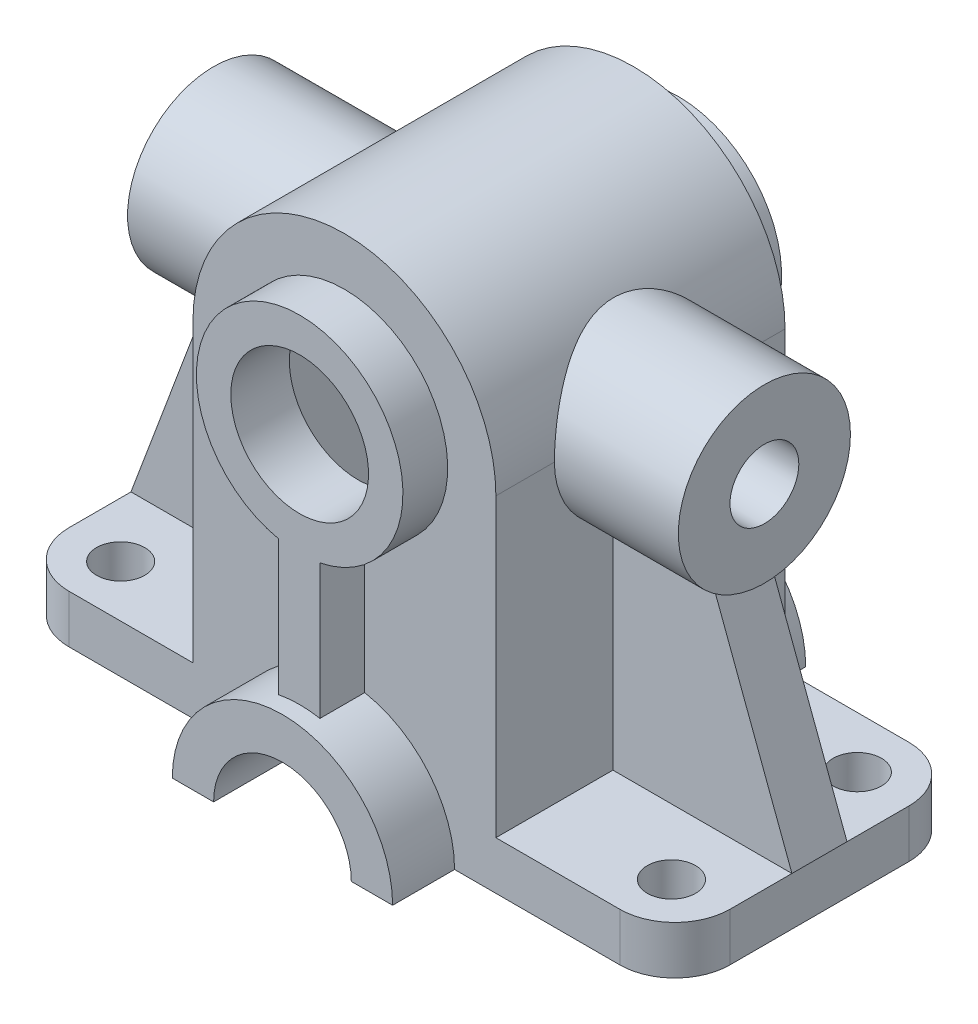
SolidWorks part; units mm, degrees
note: The reader was unsure of these and kept them because the rebuilt part matched: shared geometry of "Sketch5<3>", "Sketch1<3>".
ref_plane "Front Plane" through (0, 0, 0) normal (0, 0, 1) x (1, 0, 0)
ref_plane "Top Plane" through (0, 0, 0) normal (0, 1, 0) x (1, 0, 0)
ref_plane "Right Plane" through (0, 0, 0) normal (1, 0, 0) x (0, 0, -1)
sketch "Sketch1" plane through (0, 0, 0) normal (0, 0, 1) x (1, 0, 0)
  line L0 (-22, 0) -> (-22, -43)
  line L1 (-22, -43) -> (-48, -43)
  line L2 (-48, -43) -> (-48, -50)
  line L3 (-48, -50) -> (-10, -50)
  line L5 (48, -50) -> (10, -50)
  line L6 (48, -43) -> (48, -50)
  line L7 (22, -43) -> (48, -43)
  line L8 (22, 0) -> (22, -43)
  circle A0 centre (0, 0) radius 15
  arc A1 (22, 0) -> (-22, 0) centre (0, 0) ccw
  circle A2 centre (0, 0) radius 10
  arc A3 (16, -50) -> (-16, -50) centre (0, -50) ccw
  arc A4 (10, -50) -> (-10, -50) centre (0, -50) ccw
  dimension "D1" = 44
  dimension "D2" = 20
  dimension "D3" = 30
  dimension "D4" = 7
  dimension "D7" = 16
  dimension "D8" = 10
  dimension "D5" = 50
  dimension "D6" = 48
extrude "Boss-Extrude1" add sketch "Sketch1" along normal mid plane 42 contours A3 L5 L6 L7 L8 A1 L0 L1 L2 L3 A0 | A4 L5 A3 L3 | A0 A2
sketch "Sketch2" plane through (0, -43, 0) normal (0, 1, 0) x (1, 0, 0)
  line L0 (48, 0) -> (22, 0)
  line L1 (48, -21) -> (48, 21) construction
  line L2 (22, -21) -> (22, 21) construction
  circle A1 centre (40, 13.5) radius 3.5
  circle A2 centre (40, -13.5) radius 3.5
  dimension "D1" = 27
  dimension "D2" = 7
extrude "Cut-Extrude1" cut sketch "Sketch2" against normal blind 60 contours A1 | A2
mirror "Mirror1" about plane through (0, 0, 0) normal (1, 0, 0) of "Cut-Extrude1"
fillet "Fillet1" radius 8 4 edges at (-48, -46.5, -21) (-48, -46.5, 21) (48, -46.5, -21) (48, -46.5, 21)
sketch "Sketch5" plane through (0, 0, 21) normal (0, 0, 1) x (1, 0, 0)
  line L0 (-16.0287, -50) -> (-10, -50)
  line L1 (2.9465, -14.7078) -> (2.9465, -34.2736)
  line L2 (-3.0535, -14.6859) -> (-3.0535, -34.2941)
  line L3 (10, -50) -> (16, -50)
  arc A0 (2.9465, -14.7078) -> (-3.0535, -14.6859) centre (0, 0) ccw
  arc A1 (10, -50) -> (-10, -50) centre (0, -50) ccw
  arc A3 (16, -50) -> (-16, -50) centre (0, -50) ccw
  point P1 (0, 0)
  point P8 (0, 0)
  dimension "D2" = 15
  dimension "D3" = 16
  dimension "D4" = 10
  dimension "D1" = 6
extrude "Boss-Extrude2" add sketch "Sketch5" along normal blind 6.5
extrude "Boss-Extrude3" add sketch "Sketch5<3>" along normal blind 9
sketch "Sketch5<3>" plane through (0, 0, 21) normal (0, 0, 1) x (1, 0, 0) same geometry as "Sketch5"
mirror "Mirror2" about plane through (0, 0, 0) normal (0, 0, 1) of "Boss-Extrude3", "Boss-Extrude2"
sketch "Sketch6" plane through (0, 0, 0) normal (1, 0, 0) x (0, 0, -1)
  circle A0 centre (0, 0) radius 12.5
  dimension "D1" = 25
extrude "Boss-Extrude4" add sketch "Sketch6" along normal blind 40
sketch "Sketch7" plane through (0, 0, 0) normal (0, 0, 1) x (1, 0, 0)
  line L0 (22, -43) -> (48, -43)
  line L1 (48, -43) -> (36, -10.9553)
  line L2 (36, -10.9553) -> (22, -10.9553)
  line L3 (22, 0) -> (22, -43) construction
  line L4 (22, -10.9553) -> (22, -43)
  dimension "D1" = 14
extrude "Boss-Extrude5" add sketch "Sketch7" along normal mid plane 8
extrude "Cut-Extrude2" cut sketch "Sketch1<3>" against normal mid plane 42 contours A2
sketch "Sketch1<3>" plane through (0, 0, 0) normal (0, 0, 1) x (1, 0, 0) same geometry as "Sketch1"
sketch "Sketch8" plane through (0, 0, 0) normal (0, 1, 0) x (1, 0, 0)
  line L0 (40, 0) -> (22, 0)
  line L1 (40, -12.5) -> (40, 12.5) construction
  line L4 (40, 0) -> (40, 5)
  line L6 (40, 5) -> (24.8738, 5)
  line L7 (24.8738, 5) -> (24.8738, 4.5)
  line L8 (24.8738, 4.5) -> (23.8738, 4.5)
  line L10 (23.8738, 4.5) -> (22, 0)
  dimension "D1" = 5
  dimension "D3" = 1
revolve "Cut-Revolve1" cut sketch "Sketch8" angle 360 about L0
mirror "Mirror4" about plane through (0, 0, 0) normal (1, 0, 0) of "Cut-Revolve1", "Cut-Extrude2", "Boss-Extrude5", "Boss-Extrude4"
sketch "Sketch10" plane through (0, 0, 0) normal (0, 1, 0) x (1, 0, 0)
  line L0 (0, 19) -> (0, -19)
  line L1 (-19, -19) -> (0, -19)
  line L2 (-19, -19) -> (-19, 19)
  line L3 (-19, 19) -> (0, 19)
  line L5 (-19, -19) -> (0, 0) construction
  line L6 (-19, 19) -> (0, 0) construction
  point P0 (0, 0)
  dimension "D2" = 38
revolve "Cut-Revolve2" cut sketch "Sketch10" angle 360 about L0
sketch "Sketch11" plane through (0, 0, 0) normal (0, 1, 0) x (1, 0, 0)
  line L1 (-19, -19) -> (19, -19)
  line L2 (-19, -19) -> (-19, 19)
  line L3 (-19, 19) -> (19, 19)
  line L4 (19, -19) -> (19, 19)
  line L5 (-19, -19) -> (19, 19) construction
  line L6 (-19, 19) -> (19, -19) construction
  point P0 (0, 0)
  dimension "D1" = 38
  dimension "D2" = 38
extrude "Cut-Extrude3" cut sketch "Sketch11" against normal through all
